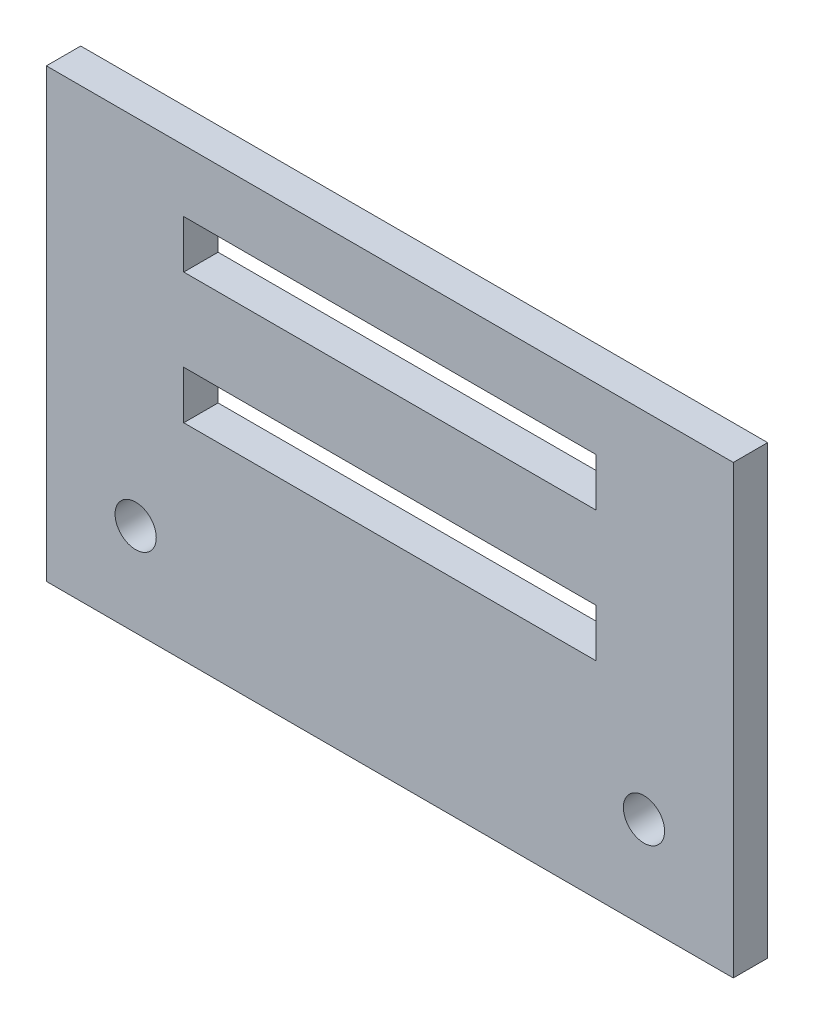
SolidWorks part; units mm, degrees
material "PBT General Purpose"
ref_plane "Front Plane" through (0, 0, 0) normal (0, 0, 1) x (1, 0, 0)
ref_plane "Top Plane" through (0, 0, 0) normal (0, 1, 0) x (1, 0, 0)
ref_plane "Right Plane" through (0, 0, 0) normal (1, 0, 0) x (0, 0, -1)
sketch "frame_outline" plane through (0, 0, 0) normal (0, 0, 1) x (1, 0, 0)
  line L123 (0.65, 0.675) -> (4.35, 0.675) construction
  line L124 (0, 0) -> (5, 0)
  line L125 (0, 0) -> (0, 3.25)
  line L126 (0, 3.25) -> (5, 3.25)
  line L127 (5, 0) -> (5, 3.25)
  line L132 (1, 1.85) -> (4, 1.85)
  line L133 (1, 1.85) -> (1, 1.5)
  line L134 (1, 1.5) -> (4, 1.5)
  line L135 (4, 1.85) -> (4, 1.5)
  line L136 (1, 2.45) -> (4, 2.45)
  line L137 (1, 2.45) -> (1, 2.8)
  line L138 (1, 2.8) -> (4, 2.8)
  line L139 (4, 2.45) -> (4, 2.8)
  circle A0 centre (0.65, 0.675) radius 0.15
  circle A1 centre (4.35, 0.675) radius 0.15
  point P12 (2.5, 1.5)
  point P13 (2.5, 0)
  point P18 (2.5, 0.675)
  point P19 (1, 1.675)
  dimension "D7" = 0.3
  dimension "D8" = 0.3
  dimension "D1" = 3
  dimension "D2" = 5
  dimension "D3" = 0.35
  dimension "D4" = 3.25
  dimension "D5" = 1.5
  dimension "D6" = 2.45
  dimension "D9" = 1.85
  dimension "D10" = 1
extrude "Boss-Extrude1" add sketch "frame_outline" along normal mid plane 0.25
equation "\"t\"= 0.25'thickness of the sheets"
equation "\"t_cf\" = 0.115'thickness of single carbon fiber layer"
equation "\"t_kapton\" = 0.025'thickness of single Kapton flex layer"
equation "\"t_fr4\" = 0.1'thickness of FR4 with copper layer"
equation "\"joint_flex\"= 0.1'Width of flextures gap"
equation "\"joint_flex_eff\"= 0.02'Width of flecture after castelation"
equation "\"joint_fold\"= 0.2'Width of folding joints for 90deg fold"
equation "\"gap_tolerance\"= 0.002'Width to have interfecence fit between carbon fiber inserts"
equation "\"assemble_angle\"= 90'Angle of assembly parts"
equation "\"D1@Boss-Extrude1\"=\"t\""
equation "\"link_lift\"= 0.5'Actuation linkage amplification for the lift motion"
equation "\"link_swing\"= 0.45'Actuation linkage amplification for the swing motion"
equation "\"D3@frame_outline\"=0.35"
